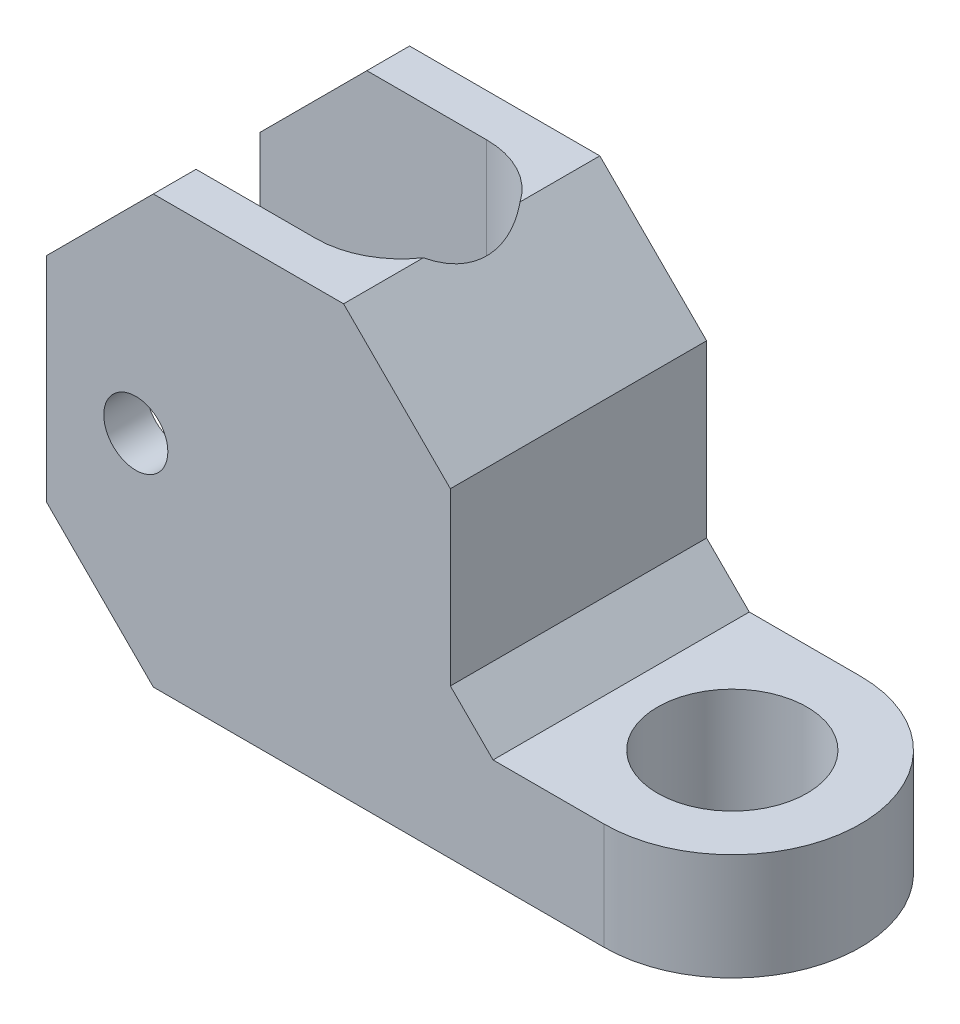
SolidWorks part; units mm, degrees
ref_plane "Front Plane" through (0, 0, 0) normal (0, 0, 1) x (1, 0, 0)
ref_plane "Top Plane" through (0, 0, 0) normal (0, 1, 0) x (1, 0, 0)
ref_plane "Right Plane" through (0, 0, 0) normal (1, 0, 0) x (0, 0, -1)
sketch "Sketch1" plane through (0, 0, 0) normal (0, 1, 0) x (1, 0, 0)
  line L0 (4, 0) -> (12, 0) construction
  line L1 (0, 6) -> (15.5, 6)
  line L2 (15.5, -6) -> (-10.6146, -6)
  line L3 (-10.6146, -6) -> (-10.6146, -4)
  line L4 (-10.6146, -4) -> (0, -4)
  line L6 (0, 4) -> (-10.6146, 4)
  line L7 (-10.6146, 4) -> (-10.6146, 6)
  line L8 (-10.6146, 6) -> (0, 6)
  arc A0 (0, -4) -> (0, 4) centre (0, 0) ccw
  circle A1 centre (15.5, 0) radius 3.5
  arc A2 (15.5, 6) -> (15.5, -6) centre (15.5, 0) cw
  point P15 (0, 0)
  dimension "D1" = 8
  dimension "D2" = 7
  dimension "D4" = 6
  dimension "D3" = 8
extrude "Boss-Extrude1" add sketch "Sketch1" along normal blind 5
sketch "Sketch2" plane through (0, 5, 0) normal (0, 1, 0) x (1, 0, 0)
  line L0 (8.296, 6) -> (8.296, -6)
  line L6 (15.5, 6) -> (-10.6146, 6)
  line L7 (-10.6146, 6) -> (-10.6146, 4)
  line L8 (-10.6146, 4) -> (0, 4)
  line L9 (0, -4) -> (-10.6146, -4)
  line L10 (-10.6146, -4) -> (-10.6146, -6)
  line L11 (-10.6146, -6) -> (15.5, -6)
  line L12 (8.296, 6) -> (-10.6146, 6)
  line L13 (-10.6146, 6) -> (-10.6146, 4)
  line L14 (-10.6146, 4) -> (0, 4)
  line L15 (0, -4) -> (-10.6146, -4)
  line L16 (-10.6146, -4) -> (-10.6146, -6)
  line L17 (-10.6146, -6) -> (8.296, -6)
  arc A2 (0, -4) -> (0, 4) centre (0, 0) ccw
  arc A3 (15.5, -6) -> (15.5, 6) centre (15.5, 0) ccw
  arc A4 (0, -4) -> (0, 4) centre (0, 0) ccw
  dimension "D1" = 0
extrude "Boss-Extrude2" add sketch "Sketch2" along normal blind 15
chamfer "Chamfer1" distance 5 angle 45 1 edges at (8.296, 20, 0)
chamfer "Chamfer2" distance 5 angle 45 4 edges at (-10.6146, 0, 5) (-10.6146, 0, -5) (-10.6146, 20, 5) (-10.6146, 20, -5)
sketch "Sketch3" plane through (0, 0, 6) normal (0, 0, 1) x (1, 0, 0)
  circle A0 centre (-6.4347, 9.8827) radius 1.5
  dimension "D1" = 3
extrude "Cut-Extrude1" cut sketch "Sketch3" against normal through all both and the other way through all
chamfer "Chamfer3" distance 2 angle 45 1 edges at (8.296, 5, 0)
